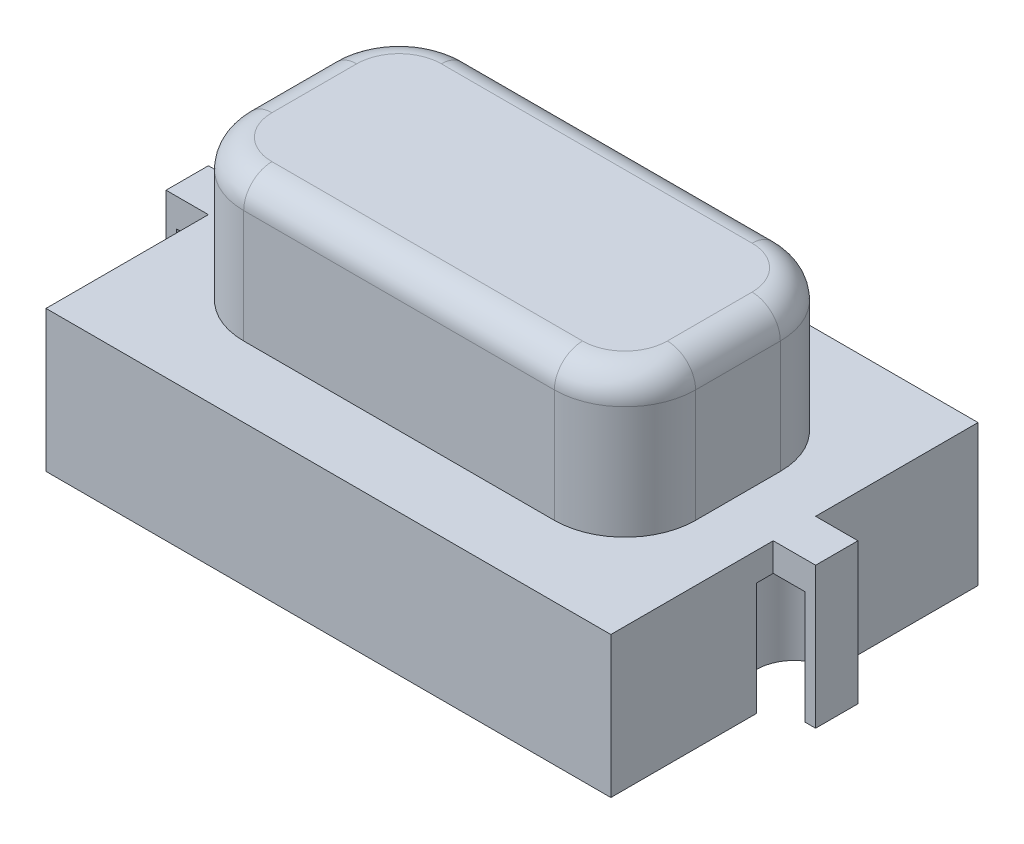
SolidWorks part; units mm, degrees
ref_plane "Front Plane" through (0, 0, 0) normal (0, 0, 1) x (1, 0, 0)
ref_plane "Top Plane" through (0, 0, 0) normal (0, 1, 0) x (1, 0, 0)
ref_plane "Right Plane" through (0, 0, 0) normal (1, 0, 0) x (0, 0, -1)
sketch "Sketch2" plane through (0, 0, 0) normal (0, 1, 0) x (1, 0, 0)
  line L0 (-5.5, -4.5) -> (5.5, -4.5) construction
  line L1 (-8.5, -1.5) -> (-8.5, 1.5) construction
  line L2 (-5.5, 4.5) -> (5.5, 4.5) construction
  line L3 (8.5, -1.5) -> (8.5, 1.5) construction
  line L4 (0, 4.5) -> (0, -4.5) construction
  line L5 (-5.5, 4) -> (5.5, 4)
  line L6 (8, -1.5) -> (8, 1.5)
  line L7 (-5.5, -4) -> (5.5, -4)
  line L8 (-8, -1.5) -> (-8, 1.5)
  line L13 (-10, 0.75) -> (-11.5, 0.75)
  line L14 (-10, 6.5) -> (10, 6.5)
  line L15 (-10, 6.5) -> (-10, -6.5)
  line L16 (-10, -6.5) -> (10, -6.5)
  line L17 (10, 6.5) -> (10, -6.5)
  line L18 (0, -6.5) -> (0, 6.5) construction
  line L19 (-10, 0) -> (10, 0) construction
  line L20 (-11.5, 0.75) -> (-11.5, -0.75)
  line L21 (-11.5, -0.75) -> (-10, -0.75)
  line L22 (-10, 0) -> (-11.5, 0) construction
  line L23 (10, 0.75) -> (11.5, 0.75)
  line L24 (11.5, 0.75) -> (11.5, -0.75)
  line L25 (11.5, -0.75) -> (10, -0.75)
  arc A0 (5.5, 4.5) -> (8.5, 1.5) centre (5.5, 1.5) cw construction
  arc A1 (5.5, -4.5) -> (8.5, -1.5) centre (5.5, -1.5) ccw construction
  arc A2 (-5.5, -4.5) -> (-8.5, -1.5) centre (-5.5, -1.5) cw construction
  arc A3 (-8.5, 1.5) -> (-5.5, 4.5) centre (-5.5, 1.5) cw construction
  arc A4 (5.5, 4) -> (8, 1.5) centre (5.5, 1.5) cw
  arc A5 (5.5, -4) -> (8, -1.5) centre (5.5, -1.5) ccw
  arc A6 (-5.5, -4) -> (-8, -1.5) centre (-5.5, -1.5) cw
  arc A7 (-8, 1.5) -> (-5.5, 4) centre (-5.5, 1.5) cw
  point P184 (0, 0)
  dimension "D3" = 3
  dimension "D6" = 20
  dimension "D1" = 17
  dimension "D2" = 9
  dimension "D5" = 13
  dimension "D7" = 1.5
  dimension "D8" = 1.5
  dimension "D4" = 0.5
extrude "Boss-Extrude1" add sketch "Sketch2" along normal blind 5 contours A7 L8 A6 L7 A5 L6 A4 L5 region at (0, 0, 0)
extrude "Boss-Extrude2" add sketch "Sketch2<3>" against normal blind 5 contours A7 L8 A6 L7 A5 L6 A4 L5 | L17 L8 A7 L5 A4 L6 A5 L7 A6 | L25 L24 L23 L17 | L20 L21 L15 L13 region at (0, 0, 0) region at (-10.75, 0, 0) region at (-9.7615, 0, -3.625) region at (10.75, 0, 0)
sketch "Sketch2<3>" plane through (0, 0, 0) normal (0, 1, 0) x (1, 0, 0) same geometry as "Sketch2"
fillet "Fillet1" radius 1 8 edges at (-7.2678, 5, 3.2678) (-8, 5, 0) (-7.2678, 5, -3.2678) (0, 5, -4) (7.2678, 5, -3.2678) (8, 5, 0) (7.2678, 5, 3.2678) (0, 5, 4)
sketch "Sketch3" plane through (0, 0, 0) normal (0, 1, 0) x (1, 0, 0)
  line L0 (-10, 0) -> (10, 0) construction
  circle A0 centre (10, 0) radius 1.35
  circle A1 centre (-10, 0) radius 1.35
  dimension "D1" = 2.7
  dimension "D2" = 20
extrude "Cut-Extrude1" cut sketch "Sketch3" along normal blind 4 from surface starting at face at (0, -5, 0)
